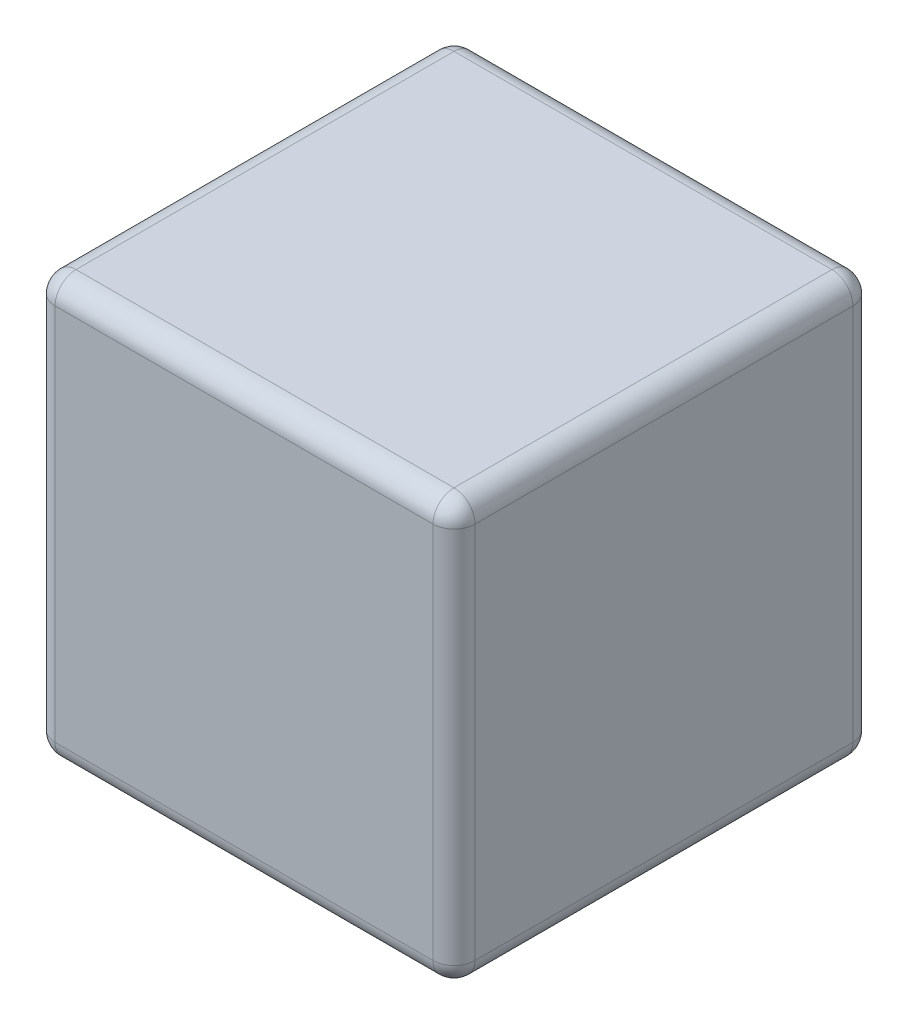
SolidWorks part; units mm, degrees
ref_plane "Front Plane" through (0, 0, 0) normal (0, 0, 1) x (1, 0, 0)
ref_plane "Top Plane" through (0, 0, 0) normal (0, 1, 0) x (1, 0, 0)
ref_plane "Right Plane" through (0, 0, 0) normal (1, 0, 0) x (0, 0, -1)
sketch "Sketch1" plane through (0, 0, 0) normal (0, 1, 0) x (1, 0, 0)
  line L1 (-5, -5) -> (5, -5)
  line L2 (-5, -5) -> (-5, 5)
  line L3 (-5, 5) -> (5, 5)
  line L4 (5, -5) -> (5, 5)
  line L5 (-5, -5) -> (5, 5) construction
  line L6 (-5, 5) -> (5, -5) construction
  point P0 (0, 0)
  dimension "D1" = 10
  dimension "D2" = 10
extrude "Boss-Extrude1" add sketch "Sketch1" along normal blind 5 and the other way blind 5 contours L4 L3 L2 L1
fillet "Fillet1" radius 0.5 12 edges at (0, -5, -5) (5, -5, 0) (5, 0, -5) (0, -5, 5) (5, 0, 5) (-5, -5, 0) (-5, 0, -5) (-5, 0, 5) (-5, 5, 0) (0, 5, -5) (5, 5, 0) (0, 5, 5)
